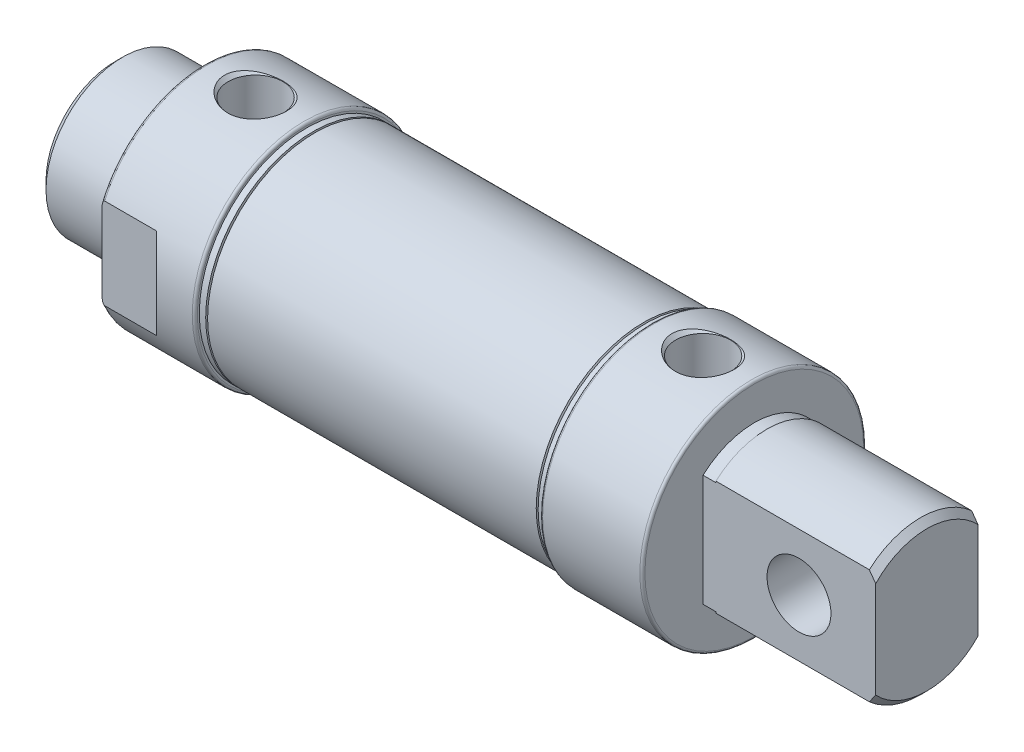
SolidWorks part; units mm, degrees
ref_plane "前视基准面" through (0, 0, 0) normal (0, 0, 1) x (1, 0, 0)
ref_plane "上视基准面" through (0, 0, 0) normal (0, 1, 0) x (1, 0, 0)
ref_plane "右视基准面" through (0, 0, 0) normal (1, 0, 0) x (0, 0, -1)
sketch "草图1" plane through (0, 0, 0) normal (0, 0, 1) x (1, 0, 0)
  line L0 (0, 0) -> (0, 10.773)
  line L1 (0, 10.773) -> (1.227, 12)
  line L2 (1.227, 12) -> (14, 12)
  line L3 (14, 12) -> (14, 17.1)
  line L4 (14.4, 17.5) -> (29.6, 17.5)
  line L5 (30, 17.1) -> (30, 16.8)
  line L6 (30, 16.8) -> (31, 16.8)
  line L7 (31, 16.8) -> (31, 16.3)
  line L8 (31, 16.3) -> (31.3, 16.8)
  line L9 (31.3, 16.8) -> (82.7, 16.8)
  line L10 (82.7, 16.8) -> (83, 16.3)
  line L11 (83, 16.3) -> (83, 16.8)
  line L12 (83, 16.8) -> (84, 16.8)
  line L13 (84, 16.8) -> (84, 17.1)
  line L14 (84.4, 17.5) -> (99.6, 17.5)
  line L15 (100, 17.1) -> (100, 0)
  line L16 (100, 0) -> (0, 0)
  line L17 (100, 0) -> (0, 0) construction
  arc A0 (14, 17.1) -> (14.4, 17.5) centre (14.4, 17.1) cw
  arc A1 (29.6, 17.5) -> (30, 17.1) centre (29.6, 17.1) cw
  arc A2 (84, 17.1) -> (84.4, 17.5) centre (84.4, 17.1) cw
  arc A3 (99.6, 17.5) -> (100, 17.1) centre (99.6, 17.1) cw
revolve "旋转1" add sketch "草图1" angle 360 about L17 reverse direction yes
cosmetic thread "装饰螺纹线1" parameters "D1"=12, "D2"=21.546
sketch "草图2" plane through (0, 0, 0) normal (0, 0, 1) x (1, 0, 0)
  line L0 (100, 0) -> (100, 11.85)
  line L1 (100, 11.85) -> (102, 11.85)
  line L2 (102, 11.85) -> (102, 12)
  line L3 (102, 12) -> (126, 12)
  line L4 (126, 12) -> (127, 11)
  line L5 (127, 11) -> (127, 0)
  line L6 (127, 0) -> (100, 0)
  line L7 (127, 0) -> (100, 0) construction
revolve "旋转2" add sketch "草图2" angle 360 about L7 reverse direction yes
cosmetic thread "装饰螺纹线2" parameters "D1"=25, "D2"=20.319
ref_plane "基准面4" through (14, 0, 0) normal (1, 0, 0) x (0, 0, -1)
ref_plane "基准面5" through (127, 0, 0) normal (1, 0, 0) x (0, 0, -1)
sketch "草图3" plane through (127, 0, 0) normal (1, 0, 0) x (0, 0, -1)
  line L0 (-18, 22) -> (-18, -22)
  line L1 (-18, -22) -> (18, -22)
  line L2 (18, -22) -> (18, 22)
  line L3 (18, 22) -> (-18, 22)
  line L4 (-8, 12) -> (-8, -12)
  line L5 (-8, -12) -> (8, -12)
  line L6 (8, -12) -> (8, 12)
  line L7 (8, 12) -> (-8, 12)
extrude "切除-拉伸1" cut sketch "草图3" against normal blind 27
ref_plane "基准面6" through (115, 0, 0) normal (1, 0, 0) x (0, 0, -1)
sketch "草图4" plane through (115, 0, 0) normal (1, 0, 0) x (0, 0, -1)
  line L0 (-8, 0) -> (-8, 5)
  line L1 (-8, 5) -> (8, 5)
  line L2 (8, 5) -> (8, 0)
  line L3 (8, 0) -> (-8, 0)
  line L4 (8, 0) -> (-8, 0) construction
revolve "切除-旋转1" cut sketch "草图4" angle 360 about L4 reverse direction yes
sketch "草图5" plane through (0, 0, 0) normal (0, 0, 1) x (1, 0, 0)
  line L0 (22, 17.5) -> (26.864, 17.5)
  line L1 (26.864, 17.5) -> (26.283, 16.919)
  line L2 (26.283, 16.919) -> (26.283, 9.5)
  line L3 (26.283, 9.5) -> (22, 9.5)
  line L4 (22, 9.5) -> (22, 17.5)
  line L5 (22, 9.5) -> (22, 17.5) construction
revolve "切除-旋转2" cut sketch "草图5" angle 360 about L5 reverse direction yes
cosmetic thread "装饰螺纹线3" parameters "D1"=8, "D2"=9.728
sketch "草图6" plane through (0, 0, 0) normal (0, 0, 1) x (1, 0, 0)
  line L0 (92, 17.5) -> (96.864, 17.5)
  line L1 (96.864, 17.5) -> (96.283, 16.919)
  line L2 (96.283, 16.919) -> (96.283, 9.5)
  line L3 (96.283, 9.5) -> (92, 9.5)
  line L4 (92, 9.5) -> (92, 17.5)
  line L5 (92, 9.5) -> (92, 17.5) construction
revolve "切除-旋转3" cut sketch "草图6" angle 360 about L5 reverse direction yes
cosmetic thread "装饰螺纹线4" parameters "D1"=8, "D2"=9.728
sketch "草图7" plane through (0, 0, 0) normal (0, 1, 0) x (1, 0, 0)
  line L0 (-4, -17.5) -> (24, -17.5)
  line L1 (24, -17.5) -> (22.5, -16)
  line L2 (22.5, -16) -> (-2, -16)
  line L3 (-2, -16) -> (-2, 16)
  line L4 (-2, 16) -> (22.5, 16)
  line L5 (22.5, 16) -> (24, 17.5)
  line L6 (24, 17.5) -> (-4, 17.5)
  line L7 (-4, 17.5) -> (-4, -17.5)
extrude "切除-拉伸2" cut sketch "草图7" along normal blind 35 and the other way blind 35
sketch "草图8" plane through (0, 0, 0) normal (0, 0, 1) x (1, 0, 0)
  line L0 (0, 0) -> (0, 6)
  line L1 (0, 6) -> (41, 6)
  line L2 (41, 6) -> (41, 16)
  line L3 (41, 16) -> (73, 16)
  line L4 (73, 16) -> (73, 0)
  line L5 (73, 0) -> (0, 0)
  line L6 (73, 0) -> (0, 0) construction
revolve "切除-旋转4" cut sketch "草图8" angle 360 about L6 reverse direction yes
ref_plane "基准面7" through (22, 0, 0) normal (1, 0, 0) x (0, 0, -1)
ref_plane "基准面8" through (0, 20.8, 0) normal (0, 1, 0) x (1, 0, 0)
ref_plane "基准面9" through (92, 0, 0) normal (1, 0, 0) x (0, 0, -1)
ref_plane "基准面10" through (6, 0, 0) normal (1, 0, 0) x (0, 0, -1)
ref_plane "基准面11" through (30, 0, 0) normal (1, 0, 0) x (0, 0, -1)
ref_plane "基准面12" through (14, 0, 0) normal (1, 0, 0) x (0, 0, -1)
ref_plane "基准面13" through (100, 0, 0) normal (1, 0, 0) x (0, 0, -1)
ref_plane "基准面14" through (108, 0, 0) normal (1, 0, 0) x (0, 0, -1)
ref_plane "基准面15" through (31, 0, 0) normal (1, 0, 0) x (0, 0, -1)
ref_plane "基准面16" through (83, 0, 0) normal (1, 0, 0) x (0, 0, -1)
ref_plane "IP_SWITCH1 XY" through (31, 0, 0) normal (-1, 0, 0) x (0, 0, 1)
ref_plane "IP_SWITCH1 XZ" through (0, 0, 0) normal (0, 1, 0) x (1, 0, 0)
ref_plane "IP_SWITCH1 YZ" through (0, 0, 0) normal (0, 0, -1) x (-1, 0, 0)
ref_axis "IP_SWITCH1 X" through (31, 0, 80.9) along (0, 0, -1)
ref_axis "IP_SWITCH1 Y" through (31, 50, 0) along (0, -1, 0)
ref_axis "IP_SWITCH1 Z" through (-80.9, 0, 0) along (1, 0, 0)
sketch3d "IP_SWITCH1"
  point P0 (31, 0, 0)
ref_plane "IP_SWITCH2 XY" through (83, 0, 0) normal (1, 0, 0) x (0, 0, -1)
ref_plane "IP_SWITCH2 XZ" through (0, 0, 0) normal (0, -1, 0) x (-1, 0, 0)
ref_plane "IP_SWITCH2 YZ" through (0, 0, 0) normal (0, 0, -1) x (-1, 0, 0)
ref_axis "IP_SWITCH2 X" through (83, 0, 80.9) along (0, 0, -1)
ref_axis "IP_SWITCH2 Y" through (83, -50, 0) along (0, 1, 0)
ref_axis "IP_SWITCH2 Z" through (80.9, 0, 0) along (-1, 0, 0)
sketch3d "IP_SWITCH2"
  point P0 (83, 0, 0)
ref_plane "body-dummy XY" through (30, 0, 0) normal (1, 0, 0) x (0, 0, -1)
ref_plane "body-dummy XZ" through (0, 0, 0) normal (0, -1, 0) x (-1, 0, 0)
ref_plane "body-dummy YZ" through (0, 0, 0) normal (0, 0, -1) x (-1, 0, 0)
ref_axis "body-dummy X" through (30, 0, 80.9) along (0, 0, -1)
ref_axis "body-dummy Y" through (30, -50, 0) along (0, 1, 0)
ref_axis "body-dummy Z" through (80.9, 0, 0) along (-1, 0, 0)
sketch3d "body-dummy"
  point P0 (30, 0, 0)
ref_plane "body-sdb XY" through (0, 0, 0) normal (0, 0, 1) x (1, 0, 0)
ref_plane "body-sdb XZ" through (0, 0, 0) normal (0, -1, 0) x (-1, 0, 0)
ref_plane "body-sdb YZ" through (115, 0, 0) normal (1, 0, 0) x (0, 0, -1)
ref_axis "body-sdb X" through (-80.9, 0, 0) along (1, 0, 0)
ref_axis "body-sdb Y" through (115, -50, 0) along (0, 1, 0)
ref_axis "body-sdb Z" through (115, 0, 80.9) along (0, 0, -1)
sketch3d "body-sdb"
  point P0 (115, 0, 0)
ref_plane "fa-body XY" through (14, 0, 0) normal (-1, 0, 0) x (0, 0, 1)
ref_plane "fa-body XZ" through (0, 0, 0) normal (0, 1, 0) x (1, 0, 0)
ref_plane "fa-body YZ" through (0, 0, 0) normal (0, 0, -1) x (-1, 0, 0)
ref_axis "fa-body X" through (14, 0, 80.9) along (0, 0, -1)
ref_axis "fa-body Y" through (14, 50, 0) along (0, -1, 0)
ref_axis "fa-body Z" through (-80.9, 0, 0) along (1, 0, 0)
sketch3d "fa-body"
  point P0 (14, 0, 0)
ref_plane "lb-body XY" through (100, 0, 0) normal (1, 0, 0) x (0, 0, -1)
ref_plane "lb-body XZ" through (0, 0, 0) normal (0, -1, 0) x (-1, 0, 0)
ref_plane "lb-body YZ" through (0, 0, 0) normal (0, 0, -1) x (-1, 0, 0)
ref_axis "lb-body X" through (100, 0, 80.9) along (0, 0, -1)
ref_axis "lb-body Y" through (100, -50, 0) along (0, 1, 0)
ref_axis "lb-body Z" through (80.9, 0, 0) along (-1, 0, 0)
sketch3d "lb-body"
  point P0 (100, 0, 0)
ref_plane "nut1-body XY" through (108, 0, 0) normal (1, 0, 0) x (0, 0, -1)
ref_plane "nut1-body XZ" through (0, 0, 0) normal (0, -1, 0) x (-1, 0, 0)
ref_plane "nut1-body YZ" through (0, 0, 0) normal (0, 0, -1) x (-1, 0, 0)
ref_axis "nut1-body X" through (108, 0, 80.9) along (0, 0, -1)
ref_axis "nut1-body Y" through (108, -50, 0) along (0, 1, 0)
ref_axis "nut1-body Z" through (80.9, 0, 0) along (-1, 0, 0)
sketch3d "nut1-body"
  point P0 (108, 0, 0)
ref_plane "nut2-body XY" through (6, 0, 0) normal (-1, 0, 0) x (0, 0, 1)
ref_plane "nut2-body XZ" through (0, 0, 0) normal (0, 1, 0) x (1, 0, 0)
ref_plane "nut2-body YZ" through (0, 0, 0) normal (0, 0, -1) x (-1, 0, 0)
ref_axis "nut2-body X" through (6, 0, 80.9) along (0, 0, -1)
ref_axis "nut2-body Y" through (6, 50, 0) along (0, -1, 0)
ref_axis "nut2-body Z" through (-80.9, 0, 0) along (1, 0, 0)
sketch3d "nut2-body"
  point P0 (6, 0, 0)
ref_plane "rod-body XY" through (0, 0, 0) normal (-1, 0, 0) x (0, 0, 1)
ref_plane "rod-body XZ" through (0, 0, 0) normal (0, 1, 0) x (1, 0, 0)
ref_plane "rod-body YZ" through (0, 0, 0) normal (0, 0, -1) x (-1, 0, 0)
ref_axis "rod-body X" through (0, 0, 80.9) along (0, 0, -1)
ref_axis "rod-body Y" through (0, 50, 0) along (0, -1, 0)
ref_axis "rod-body Z" through (-80.9, 0, 0) along (1, 0, 0)
sketch3d "rod-body"
  point P0 (0, 0, 0)
ref_plane "rod-nut XY" through (0, 0, 0) normal (-1, 0, 0) x (0, 0, 1)
ref_plane "rod-nut XZ" through (0, 0, 0) normal (0, 1, 0) x (1, 0, 0)
ref_plane "rod-nut YZ" through (0, 0, 0) normal (0, 0, -1) x (-1, 0, 0)
ref_axis "rod-nut X" through (0, 0, 80.9) along (0, 0, -1)
ref_axis "rod-nut Y" through (0, 50, 0) along (0, -1, 0)
ref_axis "rod-nut Z" through (-80.9, 0, 0) along (1, 0, 0)
sketch3d "rod-nut"
  point P0 (0, 0, 0)
